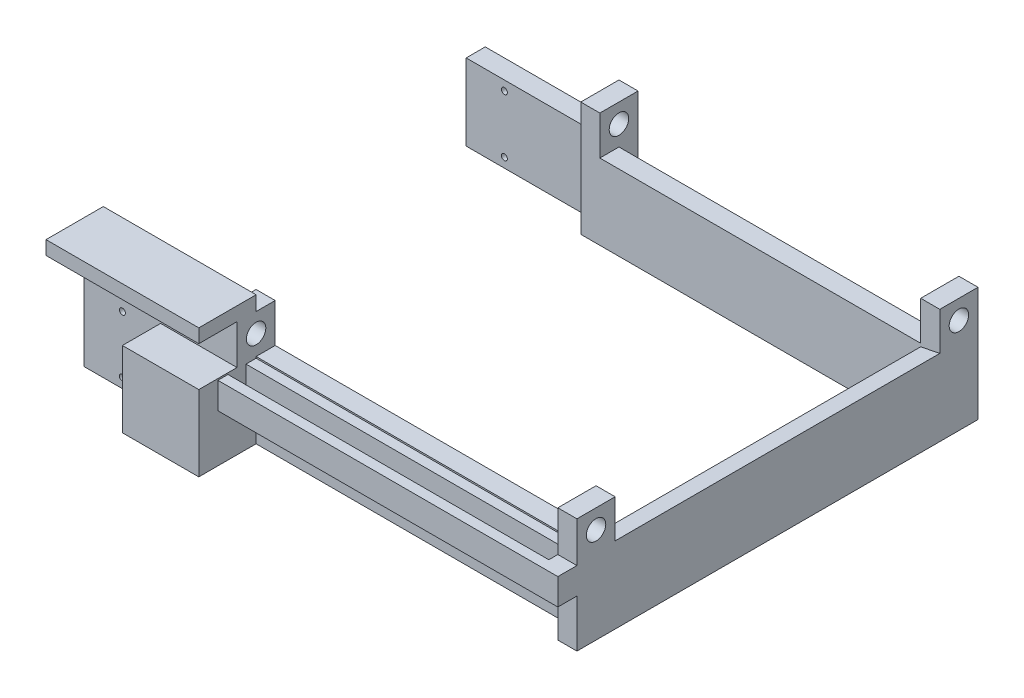
SolidWorks part; units mm, degrees
ref_plane "Front Plane" through (0, 0, 0) normal (0, 0, 1) x (1, 0, 0)
ref_plane "Top Plane" through (0, 0, 0) normal (0, 1, 0) x (1, 0, 0)
ref_plane "Right Plane" through (0, 0, 0) normal (1, 0, 0) x (0, 0, -1)
sketch "Sketch1" plane through (0, 0, 0) normal (0, 1, 0) x (1, 0, 0)
  line L0 (3.175, 114.3) -> (0, 114.3)
  line L1 (0, 0) -> (119.38, 0)
  line L2 (0, 0) -> (0, 6.35)
  line L3 (0, 120.65) -> (119.38, 120.65)
  line L4 (119.38, 0) -> (119.38, 120.65)
  line L5 (3.175, 114.3) -> (113.03, 114.3)
  line L7 (3.175, 6.35) -> (113.03, 6.35)
  line L8 (113.03, 114.3) -> (113.03, 6.35)
  line L9 (3.175, 6.35) -> (0, 6.35)
  line L10 (0, 114.3) -> (0, 120.65)
  dimension "D1" = 120.65
  dimension "D2" = 113.03
  dimension "D3" = 6.35
  dimension "D5" = 6.35
  dimension "D6" = 107.95
extrude "Boss-Extrude1" add sketch "Sketch1" along normal blind 25.4
sketch "Sketch2" plane through (0, 0, 0) normal (0, 0, 1) x (1, 0, 0)
  line L0 (119.38, 25.4) -> (113.03, 24.13)
  line L1 (113.03, 24.13) -> (113.03, 25.4)
  line L2 (0, 25.4) -> (119.38, 25.4) construction
  line L4 (113.03, 25.4) -> (119.38, 25.4)
  dimension "D2" = 1.27
extrude "Cut-Extrude1" cut sketch "Sketch2" against normal up to surface (114.3 mm away) from surface up to face at (56.515, 12.7, -114.3) starting at face at (56.515, 12.7, -6.35)
sketch "Sketch3" plane through (0, 0, 0) normal (0, 0, 1) x (1, 0, 0)
  line L0 (0, 25.4) -> (119.38, 25.4) construction
  line L1 (6.35, 25.4) -> (-44.45, 25.4)
  line L2 (6.35, 25.4) -> (6.35, 0)
  line L3 (6.35, 0) -> (-44.45, 0)
  line L4 (-44.45, 25.4) -> (-44.45, 0)
  line L5 (0, 25.4) -> (0, 0) construction
  dimension "D1" = 6.35
  dimension "D2" = 44.45
extrude "Boss-Extrude2" add sketch "Sketch3" along normal blind 6.35
extrude "Boss-Extrude3" add sketch "Sketch3<2>" against normal blind 6.35 from surface starting at face at (59.69, 12.7, -120.65)
sketch "Sketch3<2>" plane through (0, 0, 0) normal (0, 0, 1) x (1, 0, 0) same geometry as "Sketch3"
sketch "Sketch8" plane through (0, 25.4, 0) normal (0, 1, 0) x (1, 0, 0)
  line L0 (119.38, 60.325) -> (-5.0576, 60.325) construction
  line L1 (119.38, -6.35) -> (113.03, -6.35)
  line L2 (119.38, -6.35) -> (119.38, 6.35)
  line L4 (113.03, -6.35) -> (113.03, 6.35)
  line L5 (113.03, 6.35) -> (119.38, 6.35)
  line L6 (59.69, 114.3) -> (59.69, -20.9935) construction
  line L7 (0, 114.3) -> (119.38, 114.3) construction
  line L8 (119.38, 114.3) -> (119.38, 6.35) construction
  line L9 (6.35, -6.35) -> (6.35, 6.35)
  line L10 (0, 6.35) -> (6.35, 6.35)
  line L11 (0, -6.35) -> (0, 6.35)
  line L12 (0, -6.35) -> (6.35, -6.35)
  line L22 (0, 127) -> (6.35, 127)
  line L23 (0, 127) -> (0, 114.3)
  line L24 (0, 114.3) -> (6.35, 114.3)
  line L25 (6.35, 127) -> (6.35, 114.3)
  line L26 (113.03, 127) -> (113.03, 114.3)
  line L27 (119.38, 114.3) -> (113.03, 114.3)
  line L28 (119.38, 127) -> (119.38, 114.3)
  line L29 (119.38, 127) -> (113.03, 127)
  dimension "D1" = 12.7
extrude "Boss-Extrude4" add sketch "Sketch8" along normal blind 38.1 from surface starting at face at (19.5263, 0, -60.325)
sketch "Sketch9" plane through (119.38, 0, 0) normal (1, 0, 0) x (0, 0, -1)
  line L0 (-6.35, 38.1) -> (6.35, 38.1) construction
  line L3 (60.325, 36.7762) -> (60.325, 19.9574) construction
  line L4 (6.35, 38.1) -> (6.35, 0) construction
  line L5 (-6.35, 38.1) -> (-6.35, 0) construction
  circle A0 centre (0, 31.75) radius 3.2385
  circle A1 centre (120.65, 31.75) radius 3.2385
  dimension "D1" = 6.477
  dimension "D4" = 53.975
  dimension "D2" = 6.35
  dimension "D3" = 6.35
extrude "Cut-Extrude2" cut sketch "Sketch9" against normal through all both and the other way through all
sketch "Sketch10" plane through (0, 0, 6.35) normal (0, 0, 1) x (1, 0, 0)
  line L0 (0, 25.4) -> (-44.45, 25.4) construction
  line L1 (-44.45, 25.4) -> (-44.45, 0) construction
  circle A0 centre (-31.75, 22.225) radius 1
  circle A1 centre (-31.75, 3.175) radius 1
  dimension "D2" = 2
  dimension "D4" = 2
  dimension "D1" = 3.175
  dimension "D3" = 12.7
  dimension "D5" = 19.05
  dimension "D6" = 12.7
extrude "Cut-Extrude3" cut sketch "Sketch10" against normal through all
sketch "Sketch11" plane through (0, 0, 6.35) normal (0, 0, 1) x (1, 0, 0)
  line L0 (-44.45, 0) -> (6.35, 0) construction
  line L1 (6.35, 25.146) -> (-19.05, 25.146)
  line L2 (6.35, 25.146) -> (6.35, 0)
  line L3 (6.35, 0) -> (-19.05, 0)
  line L4 (-19.05, 25.146) -> (-19.05, 0)
  line L5 (0, 25.4) -> (-44.45, 25.4) construction
  dimension "D1" = 25.4
  dimension "D2" = 0.254
extrude "Boss-Extrude5" add sketch "Sketch11" along normal blind 12.7
sketch "Sketch13" plane through (0, 25.4, 0) normal (0, 1, 0) x (1, 0, 0)
  line L1 (-44.45, 0) -> (0, 0)
  line L2 (-44.45, 0) -> (-44.45, -6.35)
  line L3 (-44.45, -6.35) -> (0, -6.35)
  line L4 (0, 0) -> (0, -6.35)
extrude "Boss-Extrude6" add sketch "Sketch13" along normal up to surface (12.7 mm away) up to face at (3.175, 38.1, 0)
sketch "Sketch15" plane through (0, 0, 6.35) normal (0, 0, 1) x (1, 0, 0)
  line L0 (6.35, 25.146) -> (6.35, 38.1) construction
  line L1 (-44.45, 38.1) -> (6.35, 38.1)
  line L2 (-44.45, 38.1) -> (-44.45, 42.926)
  line L3 (-44.45, 42.926) -> (6.35, 42.926)
  line L4 (6.35, 38.1) -> (6.35, 42.926)
  point P5 (0, 0)
  dimension "D1" = 4.826
extrude "Boss-Extrude7" add sketch "Sketch15" along normal up to surface (12.7 mm away) from surface up to face at (-6.35, 12.573, 19.05) starting at face at (-32.75, 22.225, 0)
sketch "Sketch17" plane through (0, 0, 19.05) normal (0, 0, 1) x (1, 0, 0)
  line L0 (-44.45, 42.926) -> (-44.45, 38.1) construction
  line L1 (6.35, 38.1) -> (-44.45, 38.1)
  line L2 (6.35, 38.1) -> (6.35, 38.354)
  line L3 (6.35, 38.354) -> (-44.45, 38.354)
  line L4 (-44.45, 38.1) -> (-44.45, 38.354)
  dimension "D1" = 0.254
extrude "Cut-Extrude4" cut sketch "Sketch17" against normal up to surface (12.7 mm away) up to face at (-19.05, 21.082, 6.35)
sketch "Sketch19" plane through (6.35, 0, 0) normal (1, 0, 0) x (0, 0, -1)
  line L0 (-19.05, 25.146) -> (-6.35, 25.146) construction
  line L1 (-12.7, 24.638) -> (0, 24.638)
  line L2 (-12.7, 24.638) -> (-12.7, 15.875)
  line L3 (-12.7, 15.875) -> (0, 15.875)
  line L4 (0, 24.638) -> (0, 15.875)
  line L5 (-6.35, 38.1) -> (-6.35, 0) construction
  line L6 (-19.05, 0) -> (0, 0) construction
  dimension "D1" = 0.508
  dimension "D2" = 6.35
  dimension "D3" = 15.875
extrude "Boss-Extrude8" add sketch "Sketch19" along normal up to surface (113.03 mm away) up to face at (119.38, 31.75, 3.2385)
sketch "Sketch20" plane through (0, 0, 0) normal (0, 0, 1) x (1, 0, 0)
  line L1 (113.03, 25.4) -> (6.35, 25.4)
  line L2 (113.03, 25.4) -> (113.03, 25.146)
  line L3 (113.03, 25.146) -> (6.35, 25.146)
  line L19 (6.35, 25.4) -> (6.35, 25.146)
extrude "Cut-Extrude5" cut sketch "Sketch20" against normal through all
sketch "Sketch22" plane through (0, 24.638, 0) normal (0, 1, 0) x (1, 0, 0)
  line L2 (6.35, -3.35) -> (113.03, -3.35)
  line L3 (6.35, -3.35) -> (6.35, -9.35)
  line L4 (6.35, -9.35) -> (113.03, -9.35)
  line L5 (113.03, -3.35) -> (113.03, -9.35)
  line L6 (6.35, 0) -> (6.35, -12.7) construction
  line L7 (113.03, -6.35) -> (113.03, 0) construction
  point P6 (6.35, -6.35)
  point P7 (6.35, -6.35)
  dimension "D1" = 6
extrude "Cut-Extrude6" cut sketch "Sketch22" against normal through all
equation "\"tightTol\" = 0.005in"
equation "\"normTol\"= 0.01in"
equation "\"looseTol\"= 0.02in"
equation "\"D1@Sketch9\"=\"tightTol\"+0.250000in"
equation "\"D2@Sketch10\"=2mm"
equation "\"D4@Sketch10\"=2mm"
equation "\"D2@Sketch11\"=\"normTol\""
equation "\"D1@Sketch17\"=\"normTol\""
equation "\"D1@Sketch15\"=0.200000in-\"normTol\""
equation "\"D1@Sketch19\"=\"looseTol\""
equation "\"D1@Sketch22\"=6mm"
